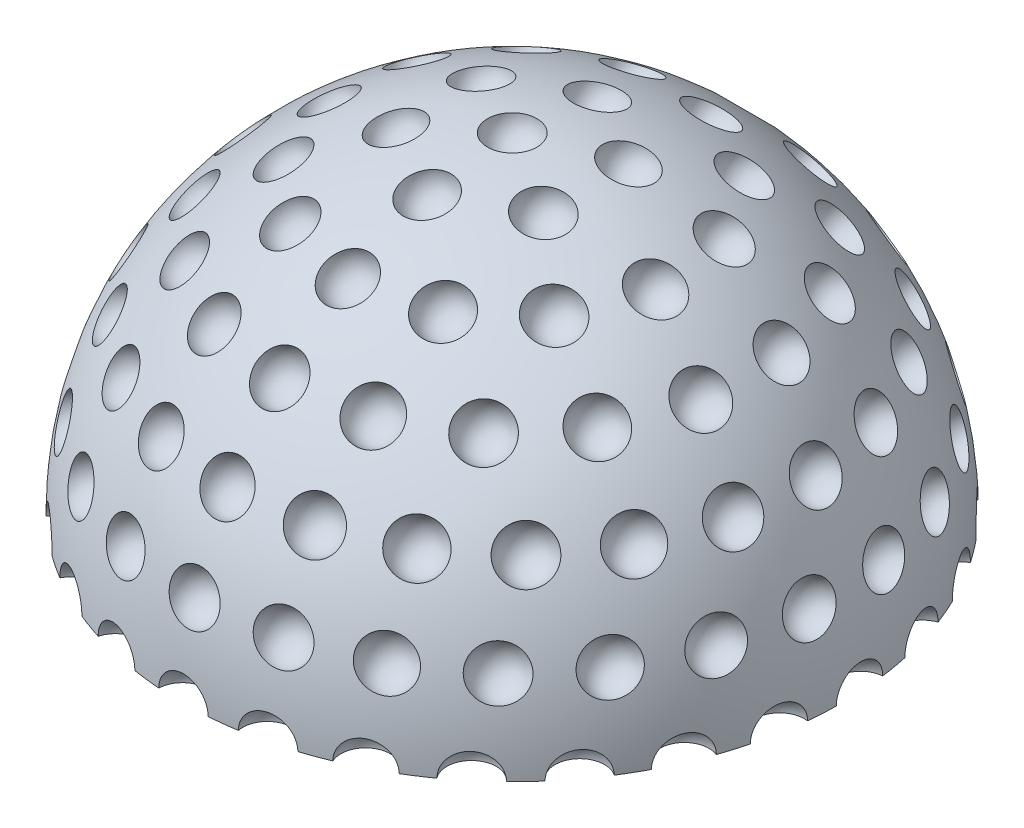
SolidWorks part; units mm, degrees
ref_plane "Front Plane" through (0, 0, 0) normal (0, 0, 1) x (1, 0, 0)
ref_plane "Top Plane" through (0, 0, 0) normal (0, 1, 0) x (1, 0, 0)
ref_plane "Right Plane" through (0, 0, 0) normal (1, 0, 0) x (0, 0, -1)
sketch "Sketch1" plane through (0, 0, 0) normal (0, 0, 1) x (1, 0, 0)
  line L0 (0, 0) -> (-50.8, 0)
  line L1 (0, 0) -> (0, 50.8)
  arc A0 (0, 50.8) -> (-50.8, 0) centre (0, 0) ccw
  dimension "D1" = 101.6
revolve "Revolve1" add sketch "Sketch1" angle 360 about L1
sketch "Sketch2" plane through (0, 0, 0) normal (0, 0, 1) x (1, 0, 0)
  line L0 (0, 54.61) -> (0, 46.99)
  arc A0 (0, 46.99) -> (0, 54.61) centre (0, 50.8) ccw
  arc A1 (50.8, 0) -> (-50.8, 0) centre (0, 0) ccw construction
  dimension "D1" = 7.62
revolve "Cut-Revolve1" cut sketch "Sketch2" angle 360 about L0
ref_axis "Axis1" through (0, 56.007, 0) along (0, -1, 0)
ref_axis "Axis2" through (-50.679, 0, 0) along (1, 0, 0)
pattern_circular "CirPattern1" count 2 every 15 about axis through (-50.679, 0, 0) along (1, 0, 0) of "Cut-Revolve1"
pattern_circular "CirPattern2" count 2 every 30 about axis through (-50.679, 0, 0) along (1, 0, 0) of "Cut-Revolve1"
pattern_circular "CirPattern3" count 2 every 45 about axis through (-50.679, 0, 0) along (1, 0, 0) of "Cut-Revolve1"
pattern_circular "CirPattern4" count 2 every 60 about axis through (-50.679, 0, 0) along (1, 0, 0) of "Cut-Revolve1"
pattern_circular "CirPattern5" count 2 every 75 about axis through (-50.679, 0, 0) along (1, 0, 0) of "Cut-Revolve1"
pattern_circular "CirPattern6" count 2 every 90 about axis through (-50.679, 0, 0) along (1, 0, 0) of "Cut-Revolve1"
pattern_circular "CirPattern8" count 6 over 360 about axis through (0, 56.007, 0) along (0, -1, 0) of "CirPattern1"
pattern_circular "CirPattern9" count 13 over 360 about axis through (0, 56.007, 0) along (0, -1, 0) of "CirPattern2"
pattern_circular "CirPattern10" count 18 over 360 about axis through (0, 56.007, 0) along (0, -1, 0) of "CirPattern3"
pattern_circular "CirPattern11" count 23 over 360 about axis through (0, 56.007, 0) along (0, -1, 0) of "CirPattern4"
pattern_circular "CirPattern12" count 25 over 360 about axis through (0, 56.007, 0) along (0, -1, 0) of "CirPattern5"
pattern_circular "CirPattern13" count 27 over 360 about axis through (0, 56.007, 0) along (0, -1, 0) of "CirPattern6"
sketch "Sketch4" plane through (0, 0, 0) normal (0, 0, 1) x (1, 0, 0)
  circle A0 centre (0, 0) radius 16.51
  dimension "D1" = 33.02
extrude "Cut-Extrude1" cut sketch "Sketch4" against normal blind 4.318 and the other way blind 4.318
